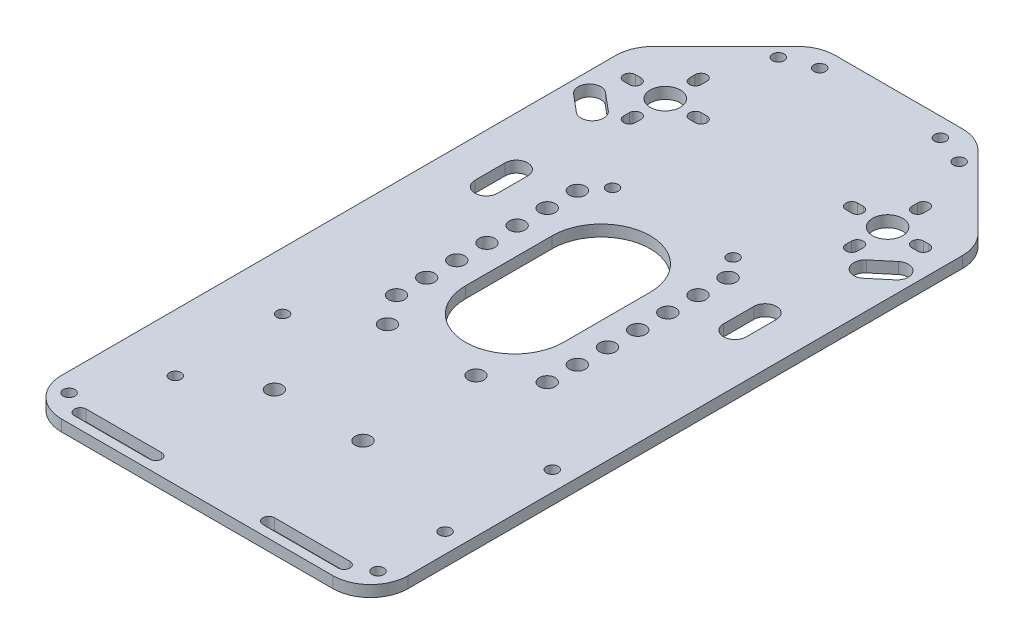
SolidWorks part; units mm, degrees
material "Thornel Mat VMA"
ref_plane "Front Plane" through (0, 0, 0) normal (0, 0, 1) x (1, 0, 0)
ref_plane "Top Plane" through (0, 0, 0) normal (0, 1, 0) x (1, 0, 0)
ref_plane "Right Plane" through (0, 0, 0) normal (1, 0, 0) x (0, 0, -1)
sketch "Sketch1" plane through (0, 0, 0) normal (0, 1, 0) x (1, 0, 0)
  line L0 (0, 0) -> (0, -275.7813) construction
  line L1 (0, 0) -> (121.6069, 0) construction
  line L2 (37.5, 0) -> (39, 0) construction
  line L3 (37.5, 1.55) -> (39, 1.55)
  line L4 (37.5, -1.55) -> (39, -1.55)
  line L5 (29.5, -8) -> (29.5, -9.5) construction
  line L6 (31.05, -8) -> (31.05, -9.5)
  line L7 (27.95, -8) -> (27.95, -9.5)
  line L8 (21.5, 0) -> (20, 0) construction
  line L9 (21.5, -1.55) -> (20, -1.55)
  line L10 (21.5, 1.55) -> (20, 1.55)
  line L11 (29.5, 8) -> (29.5, 9.5) construction
  line L12 (27.95, 8) -> (27.95, 9.5)
  line L13 (31.05, 8) -> (31.05, 9.5)
  line L14 (41, -25) -> (41, -67.0317) construction
  line L15 (-46, 32.5) -> (46, 32.5)
  line L16 (46, 32.5) -> (46, -153.73)
  line L17 (46, -153.73) -> (-46, -153.73)
  line L18 (-46, 32.5) -> (-46, -153.73)
  line L19 (-29.5, 8) -> (-29.5, 9.5) construction
  line L20 (-27.95, 8) -> (-27.95, 9.5)
  line L21 (-31.05, 8) -> (-31.05, 9.5)
  line L22 (-21.5, 0) -> (-20, 0) construction
  line L23 (-21.5, -1.55) -> (-20, -1.55)
  line L24 (-21.5, 1.55) -> (-20, 1.55)
  line L25 (-29.5, -8) -> (-29.5, -9.5) construction
  line L26 (-31.05, -8) -> (-31.05, -9.5)
  line L27 (-27.95, -8) -> (-27.95, -9.5)
  line L28 (-37.5, 0) -> (-39, 0) construction
  line L29 (-37.5, 1.55) -> (-39, 1.55)
  line L30 (-37.5, -1.55) -> (-39, -1.55)
  line L31 (0, -46.5) -> (0, -69.5) construction
  line L32 (13, -46.5) -> (13, -69.5)
  line L33 (-13, -46.5) -> (-13, -69.5)
  line L34 (0, -69.5) -> (-54.3785, -44.1429) construction
  line L35 (0, -69.5) -> (-45.0064, -85.881) construction
  line L36 (12.327, -114.5) -> (110.2373, -114.5) construction
  line L37 (5, -92.7422) -> (5, -214.7614) construction
  line L38 (29.5, 0) -> (50.8627, -25.4591) construction
  line L41 (40.7972, -8.7963) -> (36.2009, -12.653) construction
  line L42 (42.7255, -11.0944) -> (38.1293, -14.9511)
  line L43 (38.8688, -6.4981) -> (34.2725, -10.3549)
  line L44 (-40.7972, -8.7963) -> (-36.2009, -12.653) construction
  line L45 (-42.7255, -11.0944) -> (-38.1293, -14.9511)
  line L46 (-38.8688, -6.4981) -> (-34.2725, -10.3549)
  line L47 (33, -36) -> (33, -44) construction
  line L48 (36, -36) -> (36, -44)
  line L49 (30, -36) -> (30, -44)
  line L50 (-33, -36) -> (-33, -44) construction
  line L51 (-36, -36) -> (-36, -44)
  line L52 (-30, -36) -> (-30, -44)
  line L53 (15, -149.73) -> (35, -149.73) construction
  line L54 (15, -148.18) -> (35, -148.18)
  line L55 (15, -151.28) -> (35, -151.28)
  line L56 (-15, -149.73) -> (-35, -149.73) construction
  line L57 (-15, -148.18) -> (-35, -148.18)
  line L58 (-15, -151.28) -> (-35, -151.28)
  line L59 (-959, -57) -> (49041, -57) construction
  circle A0 centre (29.5, 0) radius 4
  arc A1 (37.5, 1.55) -> (37.5, -1.55) centre (37.5, 0) ccw
  arc A2 (39, -1.55) -> (39, 1.55) centre (39, 0) ccw
  arc A3 (31.05, -8) -> (27.95, -8) centre (29.5, -8) ccw
  arc A4 (27.95, -9.5) -> (31.05, -9.5) centre (29.5, -9.5) ccw
  arc A5 (21.5, -1.55) -> (21.5, 1.55) centre (21.5, 0) ccw
  arc A6 (20, 1.55) -> (20, -1.55) centre (20, 0) ccw
  arc A7 (27.95, 8) -> (31.05, 8) centre (29.5, 8) ccw
  arc A8 (31.05, 9.5) -> (27.95, 9.5) centre (29.5, 9.5) ccw
  circle A9 centre (41, -25) radius 1.55 construction
  circle A13 centre (-29.5, 0) radius 4
  arc A14 (-27.95, 8) -> (-31.05, 8) centre (-29.5, 8) cw
  arc A15 (-31.05, 9.5) -> (-27.95, 9.5) centre (-29.5, 9.5) cw
  arc A16 (-21.5, -1.55) -> (-21.5, 1.55) centre (-21.5, 0) cw
  arc A17 (-20, 1.55) -> (-20, -1.55) centre (-20, 0) cw
  arc A18 (-31.05, -8) -> (-27.95, -8) centre (-29.5, -8) cw
  arc A19 (-27.95, -9.5) -> (-31.05, -9.5) centre (-29.5, -9.5) cw
  arc A20 (-37.5, 1.55) -> (-37.5, -1.55) centre (-37.5, 0) cw
  arc A21 (-39, -1.55) -> (-39, 1.55) centre (-39, 0) cw
  circle A22 centre (16, 27.5) radius 1.55
  circle A23 centre (16, -27.5) radius 1.55
  circle A24 centre (-16, -27.5) radius 1.55
  circle A25 centre (-16, 27.5) radius 1.55
  circle A26 centre (-27.1892, -56.8215) radius 1.55 construction
  circle A27 centre (-28.1908, -79.7606) radius 1.55 construction
  circle A28 centre (28.1908, -79.7606) radius 1.55 construction
  circle A29 centre (27.1892, -56.8215) radius 1.55 construction
  arc A30 (13, -46.5) -> (-13, -46.5) centre (0, -46.5) ccw
  arc A31 (-13, -69.5) -> (13, -69.5) centre (0, -69.5) ccw
  circle A36 centre (40.79, -100.27) radius 1.55
  circle A37 centre (40.79, -128.73) radius 1.55
  circle A38 centre (-30.79, -128.73) radius 1.55
  circle A39 centre (-30.79, -100.27) radius 1.55
  circle A45 centre (41, -33) radius 1.55 construction
  circle A46 centre (41, -41) radius 1.55 construction
  circle A47 centre (41, -49) radius 1.55 construction
  circle A48 centre (41, -57) radius 1.55 construction
  circle A49 centre (41, -65) radius 1.55 construction
  circle A50 centre (41, -73) radius 1.55 construction
  circle A51 centre (41, -81) radius 1.55 construction
  circle A52 centre (-41, -81) radius 1.55 construction
  circle A53 centre (-41, -73) radius 1.55 construction
  circle A54 centre (-41, -65) radius 1.55 construction
  circle A55 centre (-41, -57) radius 1.55 construction
  circle A56 centre (-41, -49) radius 1.55 construction
  circle A57 centre (-41, -41) radius 1.55 construction
  circle A58 centre (-41, -33) radius 1.55 construction
  circle A59 centre (-41, -25) radius 1.55 construction
  arc A60 (42.7255, -11.0944) -> (38.8688, -6.4981) centre (40.7972, -8.7963) ccw
  arc A61 (34.2725, -10.3549) -> (38.1293, -14.9511) centre (36.2009, -12.653) ccw
  arc A62 (-42.7255, -11.0944) -> (-38.8688, -6.4981) centre (-40.7972, -8.7963) cw
  arc A63 (-34.2725, -10.3549) -> (-38.1293, -14.9511) centre (-36.2009, -12.653) cw
  arc A64 (36, -36) -> (30, -36) centre (33, -36) ccw
  arc A65 (30, -44) -> (36, -44) centre (33, -44) ccw
  arc A66 (-36, -36) -> (-30, -36) centre (-33, -36) cw
  arc A67 (-30, -44) -> (-36, -44) centre (-33, -44) cw
  arc A68 (15, -148.18) -> (15, -151.28) centre (15, -149.73) ccw
  arc A69 (35, -151.28) -> (35, -148.18) centre (35, -149.73) ccw
  arc A70 (-15, -148.18) -> (-15, -151.28) centre (-15, -149.73) cw
  arc A71 (-35, -151.28) -> (-35, -148.18) centre (-35, -149.73) cw
  circle A72 centre (24, 24.5) radius 1.55
  circle A73 centre (-24, 24.5) radius 1.55
  circle A74 centre (41, -146.73) radius 1.55
  circle A75 centre (-41, -146.73) radius 1.55
  point P8 (38.25, 0)
  point P18 (29.5, -8.75)
  point P25 (20.75, 0)
  point P32 (29.5, 8.75)
  point P37 (29.5, 0)
  point P50 (0, -153.73)
  point P51 (0, 32.5)
  point P55 (-29.5, 8.75)
  point P62 (-20.75, 0)
  point P69 (-29.5, -8.75)
  point P76 (-38.25, 0)
  point P98 (0, -58)
  point P145 (38.499, -10.7246)
  point P152 (-38.499, -10.7246)
  point P159 (33, -40)
  point P166 (-33, -40)
  point P173 (25, -149.73)
  point P180 (-25, -149.73)
  dimension "D1" = 8
  dimension "D2" = 1.55
  dimension "D4" = 8
  dimension "D5" = 4
  dimension "D6" = 3.1
  dimension "D7" = 25
  dimension "D8" = 41
  dimension "D9" = 59
  dimension "D10" = 3.1
  dimension "D11" = 16
  dimension "D12" = 27.5
  dimension "D13" = 13
  dimension "D15" = 30
  dimension "D18" = 46.5
  dimension "D19" = 5
  dimension "D20" = 8
  dimension "D21" = 45
  dimension "D25" = 14.23
  dimension "D26" = 35.79
  dimension "D27" = 3
  dimension "D30" = 25
  dimension "D33" = 3
  dimension "D36" = 1.55
  dimension "D40" = 8
  dimension "D41" = 3
  dimension "D42" = 5
  dimension "D43" = 7
  dimension "D3" = 1.5
  dimension "D14" = 23
  dimension "D16" = 30
  dimension "D17" = 70
  dimension "D22" = 45
  dimension "D23" = 50
  dimension "D24" = 5
  dimension "D28" = 14
  dimension "D29" = 6
  dimension "D31" = 5
  dimension "D32" = 8
  dimension "D34" = 8
  dimension "D35" = 40
  dimension "D37" = 20
  dimension "D38" = 4
  dimension "D39" = 25
extrude "Boss-Extrude1" add sketch "Sketch1" along normal blind 3
chamfer "Chamfer1" distance 25 angle 45 2 edges at (46, 1.5, -32.5) (-46, 1.5, -32.5)
fillet "Fillet1" radius 10 6 edges at (-46, 1.5, 153.73) (46, 1.5, 153.73) (46, 1.5, -7.5) (21, 1.5, -32.5) (-46, 1.5, -7.5) (-21, 1.5, -32.5)
sketch "草图1" plane through (0, 3, 0) normal (0, 1, 0) x (1, 0, 0)
  line L0 (-2.75, -1000) -> (-2.75, 49000) construction
  line L1 (-36, -153.73) -> (36, -153.73) construction
  line L2 (9, -88.73) -> (-14.5, -88.73) construction
  line L3 (9, -88.73) -> (9, -118.73) construction
  line L4 (9, -118.73) -> (-14.5, -118.73) construction
  line L5 (-14.5, -88.73) -> (-14.5, -118.73) construction
  line L6 (9, -88.73) -> (-14.5, -118.73) construction
  line L7 (9, -118.73) -> (-14.5, -88.73) construction
  line L8 (-46, 3.3579) -> (-46, -143.73) construction
  circle A0 centre (9, -88.73) radius 2.1
  circle A1 centre (9, -118.73) radius 2.1
  circle A2 centre (-14.5, -118.73) radius 2.1
  circle A3 centre (-14.5, -88.73) radius 2.1
  point P1 (-2.75, -103.73)
  dimension "D4" = 4.2
  dimension "D5" = 4.2
  dimension "D6" = 4.2
  dimension "D7" = 4.2
  dimension "D1" = 23.5
  dimension "D2" = 30
  dimension "D3" = 50
  dimension "D8" = 43.25
extrude "切除-拉伸1" cut sketch "草图1" against normal blind 10
sketch "草图2" plane through (0, 3, 0) normal (0, 1, 0) x (1, 0, 0)
  line L0 (-13, -46.5) -> (-13, -69.5) construction
  line L1 (-27.1892, -56.8215) -> (-46, -56.8215) construction
  line L2 (-46, 3.3579) -> (-46, -143.73) construction
  line L4 (-20, -56.8215) -> (-20, -30.9859) construction
  line L5 (0, -1000) -> (0, 49000) construction
  line L6 (20, -56.8215) -> (20, -30.9859) construction
  circle A3 centre (-27.1892, -56.8215) radius 1.55 construction
  circle A4 centre (-27.1892, -56.8215) radius 1.55 construction
  circle A5 centre (-20, -56.8215) radius 2.1
  circle A6 centre (-20, -48.8215) radius 2.1
  circle A7 centre (-20, -40.8215) radius 2.1
  circle A8 centre (-20, -32.8215) radius 2.1
  circle A9 centre (-20, -64.8215) radius 2.1
  circle A10 centre (-20, -72.8215) radius 2.1
  circle A11 centre (-20, -80.8215) radius 2.1
  circle A12 centre (20, -80.8215) radius 2.1
  circle A13 centre (20, -72.8215) radius 2.1
  circle A14 centre (20, -64.8215) radius 2.1
  circle A15 centre (20, -32.8215) radius 2.1
  circle A16 centre (20, -40.8215) radius 2.1
  circle A17 centre (20, -48.8215) radius 2.1
  circle A18 centre (20, -56.8215) radius 2.1
  dimension "D1" = 4.2
  dimension "D2" = 7
  dimension "D3" = 4
  dimension "D4" = 4
extrude "切除-拉伸2" cut sketch "草图2" against normal blind 10
